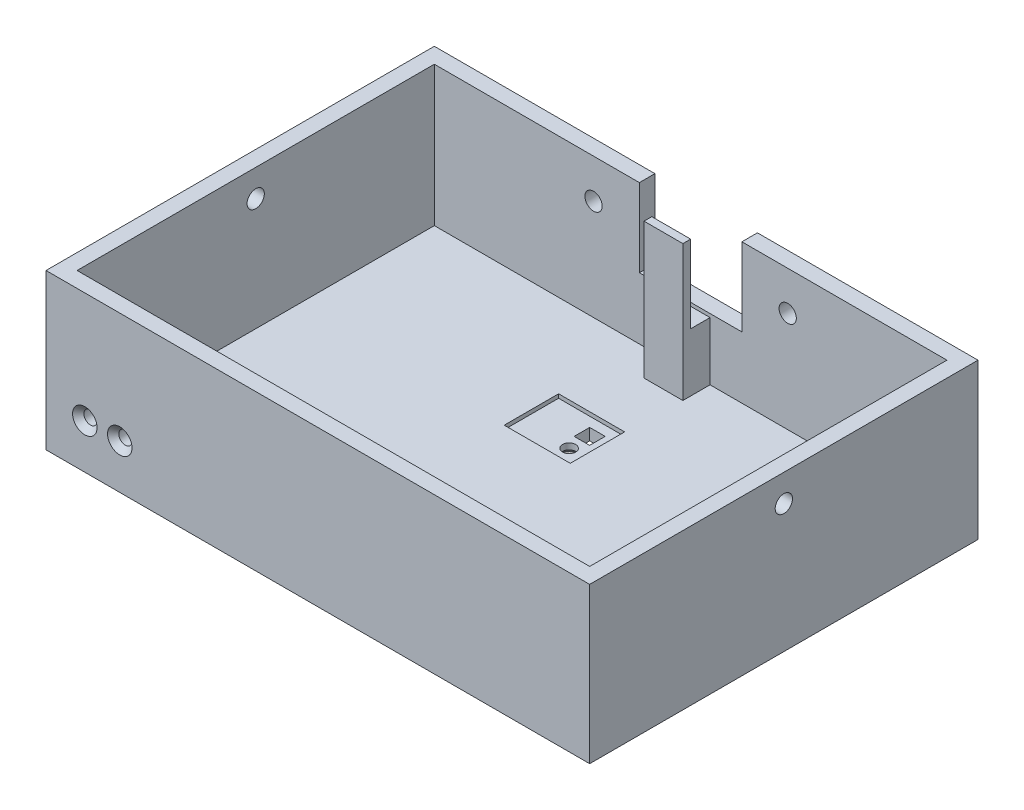
SolidWorks part; units mm, degrees
ref_plane "Спереди" through (0, 0, 0) normal (0, 0, 1) x (1, 0, 0)
ref_plane "Сверху" through (0, 0, 0) normal (0, 1, 0) x (1, 0, 0)
ref_plane "Справа" through (0, 0, 0) normal (1, 0, 0) x (0, 0, -1)
sketch "Эскиз1" plane through (0, 0, 0) normal (0, 1, 0) x (1, 0, 0)
  line L1 (70, 50) -> (-70, 50)
  line L2 (70, 50) -> (70, -50)
  line L3 (70, -50) -> (-70, -50)
  line L4 (-70, 50) -> (-70, -50)
  line L5 (70, 50) -> (-70, -50) construction
  line L6 (70, -50) -> (-70, 50) construction
  line L7 (66, 46) -> (-66, 46)
  line L8 (66, 46) -> (66, -46)
  line L9 (66, -46) -> (-66, -46)
  line L10 (-66, 46) -> (-66, -46)
  line L11 (66, 46) -> (-66, -46) construction
  line L12 (66, -46) -> (-66, 46) construction
  line L13 (-59.5, -44.6) -> (-51.5, -44.6)
  line L14 (-59.5, -44.6) -> (-59.5, -41.9)
  line L15 (-59.5, -41.9) -> (-51.5, -41.9)
  line L16 (-51.5, -44.6) -> (-51.5, -41.9)
  line L17 (-63, -46) -> (-48, -46)
  line L18 (-63, -46) -> (-63, -44.5)
  line L19 (-63, -44.5) -> (-48, -44.5)
  line L20 (-48, -46) -> (-48, -44.5)
  point P0 (0, 0)
  point P6 (0, 0)
  dimension "D1" = 140
  dimension "D2" = 100
  dimension "D3" = 4
  dimension "D4" = 4
  dimension "D5" = 1.4
  dimension "D6" = 2.7
  dimension "D7" = 8
  dimension "D8" = 15
  dimension "D9" = 3.5
  dimension "D10" = 1.5
  dimension "D11" = 3
extrude "Бобышка-Вытянуть2" add sketch "Эскиз1" along normal blind 4 contours L20 L9 L8 L7 L10 L18 L19 L14 L15 L16 | L1 L4 L3 L2 L10 L7 L8 L9 region at (68.2795, 0, 0) region at (0.1986, 0, -0.1584)
extrude "Бобышка-Вытянуть3" add sketch "Эскиз1<5>" along normal blind 2 contours L9 L20 L19 L13 L18 region at (-55.5, 0, 45.2758)
sketch "Эскиз1<5>" plane through (0, 0, 0) normal (0, 1, 0) x (1, 0, 0) same geometry as "Эскиз1"
extrude "Бобышка-Вытянуть4" add sketch "Эскиз1<6>" along normal blind 36 from surface contours L1 L4 L3 L2 L10 L7 L8 L9 region at (68.2795, 0, 0) starting at face at (-55.5, 4, 44.225)
sketch "Эскиз1<6>" plane through (0, 0, 0) normal (0, 1, 0) x (1, 0, 0) same geometry as "Эскиз1"
sketch "Эскиз2" plane through (0, 0, 46) normal (0, 0, -1) x (-1, 0, 0)
  line L0 (63, 11.5) -> (48, 11.5) construction
  line L1 (63, 4) -> (48, 4) construction
  line L2 (63, 4) -> (63, 17) construction
  line L3 (63, 17) -> (48, 17) construction
  line L4 (48, 4) -> (48, 17) construction
  line L5 (48, 2) -> (63, 2) construction
  line L6 (60, 11.5) -> (51, 11.5) construction
  circle A0 centre (60, 11.5) radius 2.025
  circle A1 centre (51, 11.5) radius 2.025
  point P12 (55.5, 11.5)
  dimension "D5" = 4.05
  dimension "D6" = 4.05
  dimension "D1" = 15
  dimension "D2" = 15
  dimension "D3" = 9.5
  dimension "D4" = 9
sketch "Эскиз4" plane through (0, 0, 50) normal (0, 0, 1) x (1, 0, 0)
  point P0 (-60, 11.5)
  point P2 (-51, 11.5)
hole_wizard "Зенковка для винта с потайной головкой M31" positions "Трехмерный эскиз2" profile "Эскиз5" countersink size "M3" standard "DIN" end condition up to next
sketch3d "Трехмерный эскиз2"
  point P0 (-51, 11.5, 50)
  point P3 (-60, 11.5, 50)
sketch "Эскиз5" plane through (-51, 11.5, 50) normal (1, 0, 0) x (0, -1, 0)
  line L0 (0, 0) -> (0, 4)
  line L1 (0, 4) -> (1.7, 4)
  line L2 (1.7, 4) -> (1.7, 1.45)
  line L3 (1.7, 1.45) -> (3.15, 0)
  line L5 (3.15, 0) -> (0, 0)
  line L6 (-1.7, 1.45) -> (-3.15, 0) construction
  line L11 (0, -6.35) -> (0, 107.95) construction
  dimension "Диаметр сквозного отверстия" = 3.4
  dimension "Глубина сквозного отверстия" = 4
  dimension "Диаметр передней зенковки" = 6.3
  dimension "Угол передней зенковки" = 90
sketch "Эскиз6" plane through (70, 0, 0) normal (1, 0, 0) x (0, 0, -1)
  line L0 (0, 40) -> (0, 33) construction
  line L1 (-50, 40) -> (50, 40) construction
  circle A0 centre (0, 33) radius 2.225
  dimension "D2" = 4.45
  dimension "D1" = 7
extrude "Вырез-Вытянуть1" cut sketch "Эскиз6" against normal up to next
mirror "Зеркальное отражение1" about plane through (0, 0, 0) normal (1, 0, 0) of "Вырез-Вытянуть1"
sketch "Эскиз7" plane through (0, 0, -50) normal (0, 0, -1) x (-1, 0, 0)
  line L0 (-13.2, 40) -> (13.2, 40)
  line L1 (70, 40) -> (-70, 40) construction
  line L2 (13.2, 40) -> (13.2, 19.9)
  line L3 (13.2, 19.9) -> (-13.2, 19.9)
  line L4 (-13.2, 19.9) -> (-13.2, 40)
  line L5 (-13.2, 19.9) -> (13.2, 40) construction
  line L19 (-16, 13.95) -> (16, 13.95) construction
  line L20 (-16, 13.95) -> (-16, 45.95) construction
  line L21 (-16, 45.95) -> (16, 45.95) construction
  line L22 (16, 13.95) -> (16, 45.95) construction
  line L23 (-16, 13.95) -> (16, 45.95) construction
  line L24 (-16, 45.95) -> (16, 13.95) construction
  line L28 (-16, 29.95) -> (-25, 29.95) construction
  line L29 (0, 13.95) -> (0, 47.2271) construction
  line L30 (16, 29.95) -> (25, 29.95) construction
  circle A0 centre (-25, 29.95) radius 2.225
  circle A1 centre (25, 29.95) radius 2.225
  point P5 (0, 40)
  point P28 (-25, 29.95)
  dimension "D9" = 4.45
  dimension "D1" = 26.4
  dimension "D2" = 20.1
  dimension "D7" = 32
  dimension "D8" = 9
extrude "Вырез-Вытянуть3" cut sketch "Эскиз7" against normal up to next contours L4 L0 L2 L3
extrude "Вырез-Вытянуть6" cut sketch "Эскиз7<9>" against normal up to next contours A0 | A1 region at (25, 29.95, -50)
sketch "Эскиз7<9>" plane through (0, 0, -50) normal (0, 0, -1) x (-1, 0, 0) same geometry as "Эскиз7"
sketch "Эскиз15" plane through (0, 0, 0) normal (0, -1, 0) x (1, 0, 0)
  line L0 (0, -50) -> (0, -20) construction
  line L1 (70, -50) -> (-70, -50) construction
  line L2 (0, -17.5) -> (0, -14.7) construction
  line L3 (-2.5, -22.5) -> (2.5, -22.5) construction
  line L4 (-2.5, -22.5) -> (-2.5, -17.5) construction
  line L5 (-2.5, -17.5) -> (2.5, -17.5) construction
  line L6 (2.5, -22.5) -> (2.5, -17.5) construction
  line L7 (-2.5, -22.5) -> (2.5, -17.5) construction
  line L8 (-2.5, -17.5) -> (2.5, -22.5) construction
  line L9 (-2, -22) -> (2, -22)
  line L10 (-2, -22) -> (-2, -18)
  line L11 (-2, -18) -> (2, -18)
  line L12 (2, -22) -> (2, -18)
  line L13 (-2, -22) -> (2, -18) construction
  line L14 (-2, -18) -> (2, -22) construction
  line L15 (-10.5, -22.5) -> (2.5, -12.5) construction
  line L16 (2.5, -22.5) -> (-10.5, -22.5) construction
  line L17 (2.5, -22.5) -> (2.5, -12.5) construction
  line L18 (2.5, -12.5) -> (-10.5, -12.5) construction
  line L19 (-10.5, -22.5) -> (-10.5, -12.5) construction
  line L21 (-12.5, -24.5) -> (4.5, -24.5)
  line L22 (-12.5, -24.5) -> (-12.5, -10.5)
  line L23 (-12.5, -10.5) -> (4.5, -10.5)
  line L24 (4.5, -24.5) -> (4.5, -10.5)
  line L25 (-12.5, -24.5) -> (4.5, -10.5) construction
  line L26 (-12.5, -10.5) -> (4.5, -24.5) construction
  point P18 (-4, -17.5)
  dimension "D1" = 30
  dimension "D2" = 5
  dimension "D3" = 4
  dimension "D4" = 2.8
  dimension "D5" = 13
  dimension "D6" = 10
  dimension "D7" = 17
  dimension "D8" = 14
hole_wizard "Зенковка для винта с потайной головкой M33" positions "Трехмерный эскиз8" profile "Эскиз16" countersink size "M3" standard "DIN" end condition up to next
sketch3d "Трехмерный эскиз8"
  point P0 (0, 0, -14.7)
sketch "Эскиз16" plane through (0, 0, -14.7) normal (1, 0, 0) x (0, 0, -1)
  line L0 (0, 0) -> (0, 4)
  line L1 (0, 4) -> (1.7, 4)
  line L2 (1.7, 4) -> (1.7, 1.45)
  line L3 (1.7, 1.45) -> (3.15, 0)
  line L5 (3.15, 0) -> (0, 0)
  line L6 (-1.7, 1.45) -> (-3.15, 0) construction
  line L11 (0, -6.35) -> (0, 107.95) construction
  dimension "Диаметр сквозного отверстия" = 3.4
  dimension "Глубина сквозного отверстия" = 4
  dimension "Диаметр передней зенковки" = 6.3
  dimension "Угол передней зенковки" = 90
extrude "Вырез-Вытянуть8" cut sketch "Эскиз15" against normal up to next contours L9 L12 L11 L10 region at (0, 0, -20)
extrude "Вырез-Вытянуть9" cut sketch "Эскиз15<4>" against normal up to next from offset 3 offset against normal yes
sketch "Эскиз15<4>" plane through (0, 0, 0) normal (0, -1, 0) x (1, 0, 0) same geometry as "Эскиз15"
sketch "Эскиз20" plane through (0, 0, 0) normal (0, -1, 0) x (1, 0, 0)
  line L0 (0, -50) -> (0, -46) construction
  line L1 (70, -50) -> (-70, -50) construction
  line L2 (-5, -46) -> (5, -46)
  line L4 (5, -46) -> (-5, -46)
  line L5 (5, -46) -> (5, -39)
  line L6 (5, -39) -> (-5, -39)
  line L7 (-5, -46) -> (-5, -39)
  line L8 (5, -39) -> (-5, -39)
  line L9 (5, -39) -> (5, -41)
  line L10 (5, -41) -> (-5, -41)
  line L11 (-5, -39) -> (-5, -41)
  point P8 (0, -46)
  dimension "D1" = 4
  dimension "D2" = 10
  dimension "D3" = 7
  dimension "D4" = 2
extrude "Бобышка-Вытянуть7" add sketch "Эскиз20" against normal blind 15 from surface contours L5 L10 L7 L2 L4 | L10 L5 L6 L7 region at (0, 0, -43.5) region at (0, 0, -40) starting at face at (-4, 4, -17.5)
extrude "Бобышка-Вытянуть8" add sketch "Эскиз20<3>" against normal blind 20 from surface contours L10 L5 L6 L7 region at (0, 0, -40) starting at face at (0, 19, -42.5)
sketch "Эскиз20<3>" plane through (0, 0, 0) normal (0, -1, 0) x (1, 0, 0) same geometry as "Эскиз20"
sketch "Эскиз21" plane through (0, 0, 0) normal (0, -1, 0) x (1, 0, 0)
  line L0 (0, 50) -> (0, 30) construction
  line L1 (70, 50) -> (-70, 50) construction
  line L2 (-35, 30) -> (35, 30) construction
  text T0 "MADE BY \r\nFEANOR19 & TIFOMEI" font "Century Gothic" height in points 14
  point P8 (0, 30)
  dimension "D1" = 20
  dimension "D2" = 70
extrude "Вырез-Вытянуть10" cut sketch "Эскиз21" against normal blind 1
